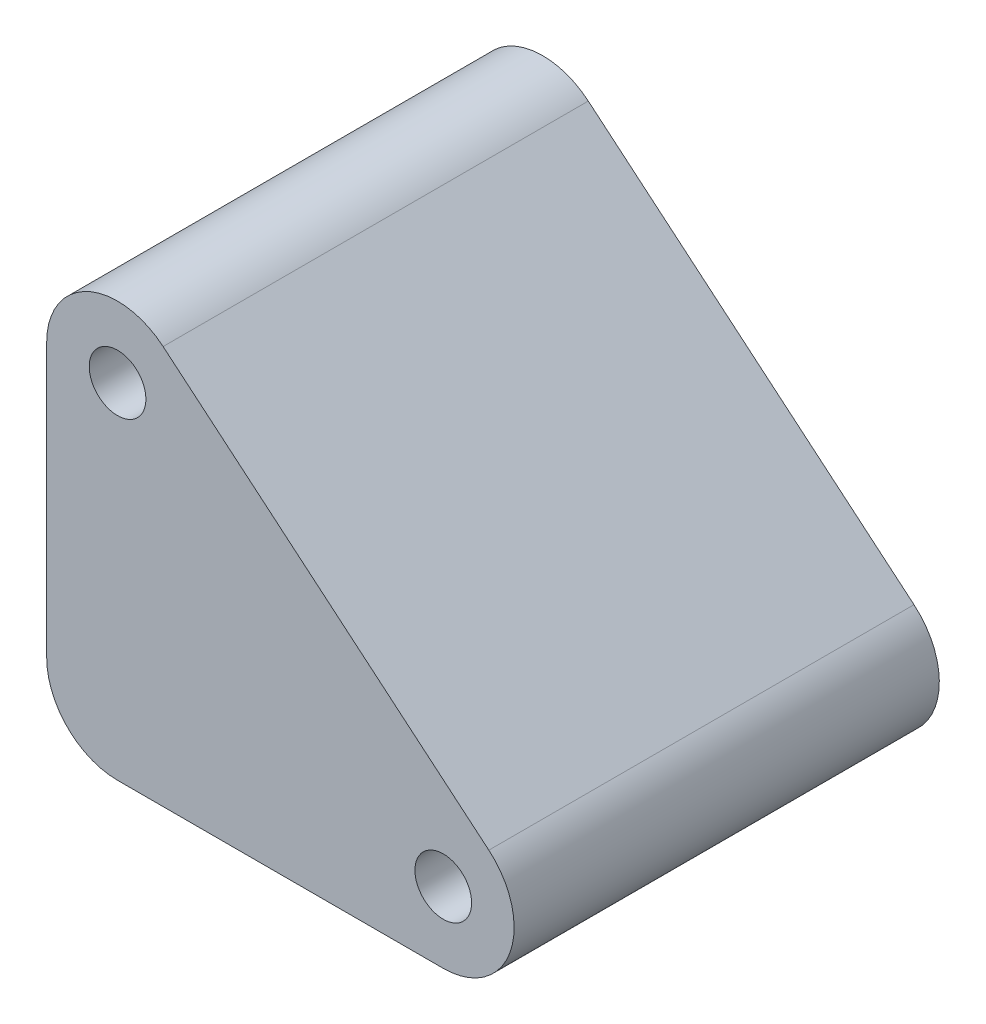
SolidWorks part; units mm, degrees
ref_plane "Front Plane" through (0, 0, 0) normal (0, 0, 1) x (1, 0, 0)
ref_plane "Top Plane" through (0, 0, 0) normal (0, 1, 0) x (1, 0, 0)
ref_plane "Right Plane" through (0, 0, 0) normal (1, 0, 0) x (0, 0, -1)
sketch "Sketch1" plane through (0, 0, 0) normal (0, 0, 1) x (1, 0, 0)
  line L3 (-250.7301, 64.8961) -> (-227.7488, 45.6125) construction
  line L4 (-230.9627, 36.7822) -> (-253.9441, 36.7822) construction
  line L5 (-258.9441, 41.7822) -> (-258.9441, 61.0659) construction
  line L6 (-250.7301, 64.8961) -> (-227.7488, 45.6125)
  line L7 (-230.9627, 36.7822) -> (-253.9441, 36.7822)
  line L8 (-258.9441, 41.7822) -> (-258.9441, 61.0659)
  circle A7 centre (-253.9441, 61.0659) radius 2 construction
  circle A8 centre (-230.9627, 41.7822) radius 2 construction
  arc A9 (-230.9627, 36.7822) -> (-227.7488, 45.6125) centre (-230.9627, 41.7822) ccw construction
  arc A10 (-258.9441, 41.7822) -> (-253.9441, 36.7822) centre (-253.9441, 41.7822) ccw construction
  arc A11 (-250.7301, 64.8961) -> (-258.9441, 61.0659) centre (-253.9441, 61.0659) ccw construction
  circle A12 centre (-253.9441, 61.0659) radius 2
  circle A13 centre (-230.9627, 41.7822) radius 2
  arc A14 (-230.9627, 36.7822) -> (-227.7488, 45.6125) centre (-230.9627, 41.7822) ccw
  arc A15 (-258.9441, 41.7822) -> (-253.9441, 36.7822) centre (-253.9441, 41.7822) ccw
  arc A16 (-250.7301, 64.8961) -> (-258.9441, 61.0659) centre (-253.9441, 61.0659) ccw
extrude "Boss-Extrude1" add sketch "Sketch1" along normal blind 15 and the other way blind 15
